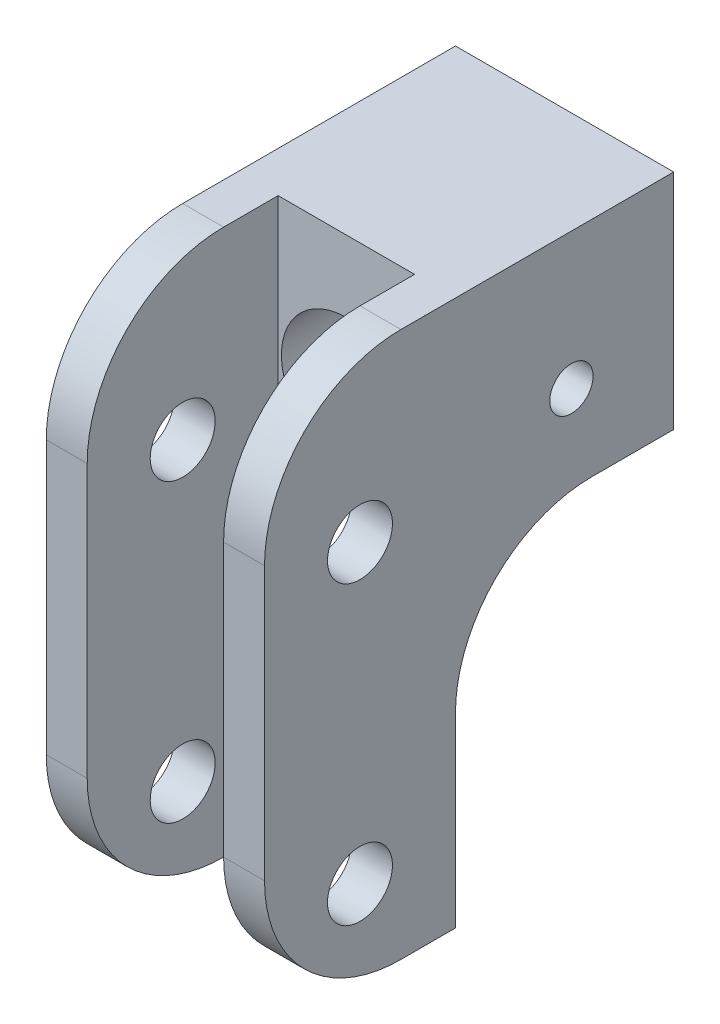
SolidWorks part; units mm, degrees
material "Plain Carbon Steel"
ref_plane "Front" through (0, 0, 0) normal (0, 0, 1) x (1, 0, 0)
ref_plane "Top" through (0, 0, 0) normal (0, 1, 0) x (1, 0, 0)
ref_plane "Right" through (0, 0, 0) normal (1, 0, 0) x (0, 0, -1)
sketch "Sketch1" plane through (0, 0, 0) normal (0, 0, 1) x (1, 0, 0)
  line L0 (0, 0) -> (0, 10) construction
  line L5 (8, -30) -> (8, 10)
  line L6 (8, 10) -> (-8, 10)
  line L7 (-8, 10) -> (-8, -30)
  line L8 (-8, -30) -> (8, -30)
  circle A3 centre (0, 0) radius 2.6 construction
  dimension "D2" = 16
  dimension "D4" = 5.2
  dimension "D6" = 10
  dimension "D7" = 40
extrude "Boss-Extrude1" add sketch "Sketch1" along normal blind 30
hole_wizard "3/8 (0.3750) Dowel Hole1" positions "Sketch2" profile "Sketch3" hole size "3/8" standard "ANSI Inch" end condition through all
sketch "Sketch2" plane through (0, 0, 30) normal (0, 0, 1) x (1, 0, 0)
  point P0 (0, 0)
sketch "Sketch3" plane through (0, 0, 30) normal (1, 0, 0) x (0, -1, 0)
  line L0 (0, 0) -> (0, 30)
  line L1 (0, 30) -> (4.7625, 30)
  line L2 (4.7625, 30) -> (4.7625, 0)
  line L5 (4.7625, 0) -> (0, 0)
  line L11 (0, -6.35) -> (0, 107.95) construction
  dimension "Thru Hole Dia." = 9.525
  dimension "Thru Hole Depth" = 30
hole_wizard "1/8 (0.1250) Dowel Hole1" positions "Sketch4" profile "Sketch5" hole size "1/8" standard "ANSI Inch" end condition through all
sketch "Sketch4" plane through (-8, 0, 0) normal (-1, 0, 0) x (0, 0, 1)
  line L0 (7.5, 10) -> (7.5, 0) construction
  line L2 (30, 10) -> (0, 10) construction
  point P0 (7.5, 0)
  dimension "D1" = 7.5
sketch "Sketch5" plane through (-8, 0, 7.5) normal (0, 1, 0) x (0, 0, 1)
  line L0 (0, 0) -> (0, 16)
  line L1 (0, 16) -> (1.5875, 16)
  line L2 (1.5875, 16) -> (1.5875, 0)
  line L5 (1.5875, 0) -> (0, 0)
  line L11 (0, -6.35) -> (0, 107.95) construction
  dimension "Thru Hole Dia." = 3.175
  dimension "Thru Hole Depth" = 16
sketch "Sketch7" plane through (0, 0, 30) normal (0, 0, 1) x (1, 0, 0)
  line L0 (8, 10) -> (-8, 10) construction
  line L1 (5, 10) -> (-5, 10)
  line L2 (5, 10) -> (5, -30)
  line L3 (5, -30) -> (-5, -30)
  line L4 (-5, 10) -> (-5, -30)
  line L5 (0, 0) -> (0, 10) construction
  line L6 (-8, -30) -> (8, -30) construction
  dimension "D1" = 10
extrude "Cut-Extrude1" cut sketch "Sketch7" against normal offset from surface (14 mm away) 16 up to face at (4.7625, 0, 0)
hole_wizard "3/16 (0.1875) Diameter Hole1" positions "Sketch8" profile "Sketch9" hole size "3/16" standard "ANSI Inch" end condition through all
sketch "Sketch8" plane through (-8, 0, 0) normal (-1, 0, 0) x (0, 0, 1)
  line L0 (23, -23.7) -> (23, -2) construction
  line L1 (23, -2) -> (16, -2) construction
  line L3 (16, 10) -> (16, -30) construction
  line L4 (30, 10) -> (0, 10) construction
  point P0 (23, -2)
  point P2 (23, -23.7)
  dimension "D1" = 7
  dimension "D2" = 21.7
  dimension "D3" = 12
sketch "Sketch9" plane through (-8, -2, 23) normal (0, 1, 0) x (0, 0, 1)
  line L0 (0, 0) -> (0, 16)
  line L1 (0, 16) -> (2.3812, 16)
  line L2 (2.3812, 16) -> (2.3812, 0)
  line L5 (2.3812, 0) -> (0, 0)
  line L11 (0, -6.35) -> (0, 107.95) construction
  dimension "Thru Hole Dia." = 4.7625
  dimension "Thru Hole Depth" = 16
sketch "Sketch10" plane through (0, 0, 0) normal (0, 0, -1) x (-1, 0, 0)
  line L0 (8, 10) -> (8, -30) construction
  line L1 (-8, -30) -> (8, -30)
  line L2 (-8, -30) -> (-8, -6.35)
  line L3 (-8, -6.35) -> (8, -6.35)
  line L4 (8, -30) -> (8, -6.35)
  dimension "D1" = 6.35
extrude "Cut-Extrude2" cut sketch "Sketch10" against normal up to surface (16 mm away) up to face at (0, -10, 16)
fillet "Fillet1" radius 10 4 edges at (-6.5, -30, 30) (6.5, -30, 30) (-6.5, 10, 30) (6.5, 10, 30)
fillet "Fillet2" radius 10 2 edges at (6.5, -6.35, 16) (-6.5, -6.35, 16)
